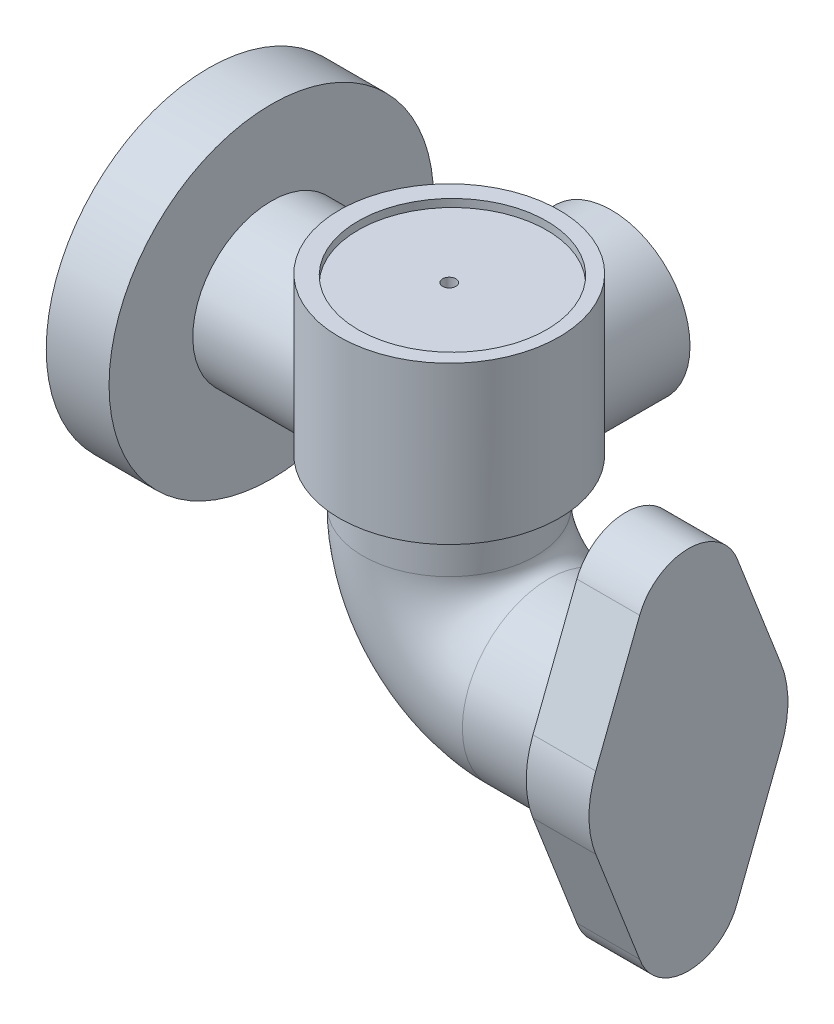
SolidWorks part; units mm, degrees
ref_plane "Front Plane" through (0, 0, 0) normal (0, 0, 1) x (1, 0, 0)
ref_plane "Top Plane" through (0, 0, 0) normal (0, 1, 0) x (1, 0, 0)
ref_plane "Right Plane" through (0, 0, 0) normal (1, 0, 0) x (0, 0, -1)
sketch "Sketch2" plane through (0, 0, 0) normal (0, 0, 1) x (1, 0, 0)
  line L0 (0, 0) -> (0, 620)
  line L1 (0, 620) -> (240, 620)
  line L2 (240, 620) -> (240, 300)
  line L3 (240, 300) -> (920, 300)
  line L4 (920, 300) -> (920, 0)
  line L5 (920, 0) -> (0, 0) construction
  line L6 (0, 0) -> (920, 0)
  dimension "D1" = 300
  dimension "D2" = 620
  dimension "D3" = 240
  dimension "D4" = 920
revolve "Revolve1" add sketch "Sketch2" angle 360 about L5
sketch "Sketch4" plane through (920, 0, 0) normal (1, 0, 0) x (0, 0, -1)
  line L0 (0, 400) -> (0, -200)
  line L1 (0, 400) -> (420, 400)
  line L2 (0, 400) -> (0, -200) construction
  line L3 (0, -200) -> (420, -200)
  line L4 (420, 400) -> (420, -200)
  dimension "D1" = 420
  dimension "D2" = 600
  dimension "D3" = 400
revolve "Revolve2" add sketch "Sketch4" angle 360 about L2
sketch "Sketch5" plane through (0, -200, 0) normal (0, -1, 0) x (1, 0, 0)
  circle A0 centre (920, 0) radius 330
  arc A1 (564.4722, -223.6068) -> (564.4722, 223.6068) centre (920, 0) ccw construction
  dimension "D1" = 660
sketch "Sketch6" plane through (0, 0, 0) normal (0, 0, 1) x (1, 0, 0)
  line L0 (920, -200) -> (920, -370)
  line L1 (1300, -750) -> (1593.9573, -750)
  arc A0 (920, -370) -> (1300, -750) centre (1300, -370) ccw
  dimension "D2" = 380
  dimension "D1" = 750
sweep "Sweep1" add profiles "Sketch5" path "Sketch6"
sketch "Sketch8" plane through (1593.9573, 0, 0) normal (1, 0, 0) x (0, 0, -1)
  line L0 (0, -253.2443) -> (0, -453.2443) construction
  line L1 (0, -750) -> (0, -1050) construction
  line L2 (-186.4083, -180.7741) -> (-354.1758, -612.3066)
  line L3 (186.4083, -180.7741) -> (354.1758, -612.3066)
  line L4 (586.6859, -750) -> (380, -750) construction
  line L5 (186.4083, -1319.2259) -> (354.1758, -887.6934)
  line L6 (-186.4083, -1319.2259) -> (-354.1758, -887.6934)
  line L7 (0, -750) -> (-586.6859, -750) construction
  arc A0 (-354.1758, -612.3066) -> (-354.1758, -887.6934) centre (0, -750) ccw
  arc A2 (-186.4083, -1319.2259) -> (186.4083, -1319.2259) centre (0, -1253.2443) ccw
  arc A3 (186.4083, -180.7741) -> (-186.4083, -180.7741) centre (0, -253.2443) ccw
  arc A4 (354.1758, -887.6934) -> (354.1758, -612.3066) centre (0, -750) ccw
  point P6 (0, -253.2443)
  point P14 (0, -750)
  dimension "D1" = 760
  dimension "D3" = 1000
extrude "Boss-Extrude1" add sketch "Sketch8" along normal blind 240 separate body
ref_plane "Plane1" through (920, 0, 0) normal (1, 0, 0) x (0, 0, -1)
sketch "Sketch12" plane through (920, 0, 0) normal (1, 0, 0) x (0, 0, -1)
  line L0 (0, 0) -> (620, 0)
  line L1 (620, 300) -> (0, 300)
  line L2 (620, 300) -> (620, 0)
  line L3 (620, 0) -> (0, 0) construction
  line L4 (0, 300) -> (0, 0)
  line L5 (620, 300) -> (0, 0) construction
  line L6 (620, 0) -> (0, 300) construction
  point P0 (310, 150)
  dimension "D1" = 300
  dimension "D2" = 620
revolve "Revolve3" add sketch "Sketch12" angle 360 about L0
sketch "Sketch13" plane through (0, 400, 0) normal (0, 1, 0) x (1, 0, 0)
  circle A0 centre (932.0854, 0) radius 360
  dimension "D1" = 720
extrude "Cut-Extrude1" cut sketch "Sketch13" against normal blind 30
hole_wizard "M56 Tapped Hole1" positions "Sketch14" profile "Sketch15" tap size "M56" standard "ISO"
sketch "Sketch14" plane through (0, 370, 0) normal (0, 1, 0) x (1, 0, 0)
  point P0 (920, 0)
cosmetic thread "Hole Thread1" parameters "D1"=2200, "D2"=56
sketch "Sketch15" plane through (920, 370, 0) normal (1, 0, 0) x (0, 0, 1)
  line L0 (0, 0) -> (0, 235.1717)
  line L1 (0, 235.1717) -> (25.25, 220)
  line L2 (25.25, 220) -> (25.25, 0)
  line L5 (25.25, 0) -> (0, 0)
  line L10 (0, 235.1717) -> (-25.25, 220) construction
  line L11 (0, -6.35) -> (0, 107.95) construction
  dimension "Tap Drill Dia." = 50.5
  dimension "Tap Drill Depth" = 220
  dimension "Drill Angle" = 118
